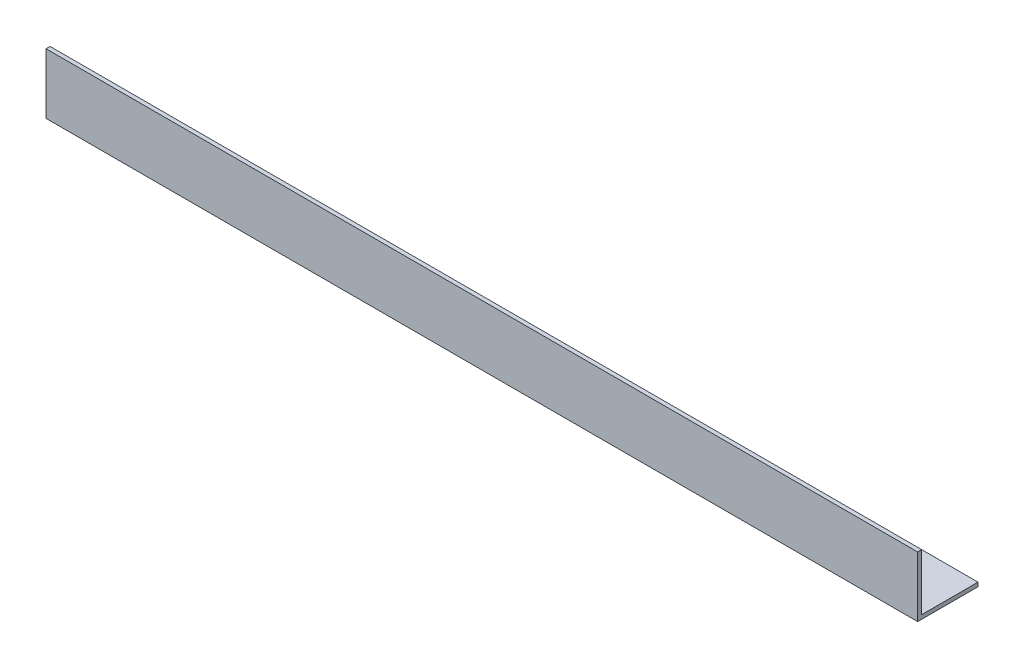
SolidWorks part; units mm, degrees
ref_plane "Спереди" through (0, 0, 0) normal (0, 0, 1) x (1, 0, 0)
ref_plane "Сверху" through (0, 0, 0) normal (0, 1, 0) x (1, 0, 0)
ref_plane "Справа" through (0, 0, 0) normal (1, 0, 0) x (0, 0, -1)
sketch "Эскиз1" plane through (0, 0, 0) normal (1, 0, 0) x (0, 0, -1)
  line L0 (0, 0) -> (0, 45)
  line L1 (0, 0) -> (45, 0)
extrude "Вытянуть-Тонкостенный1" add sketch "Эскиз1" along normal blind 650 thin thin type one direction reverse wall 3
